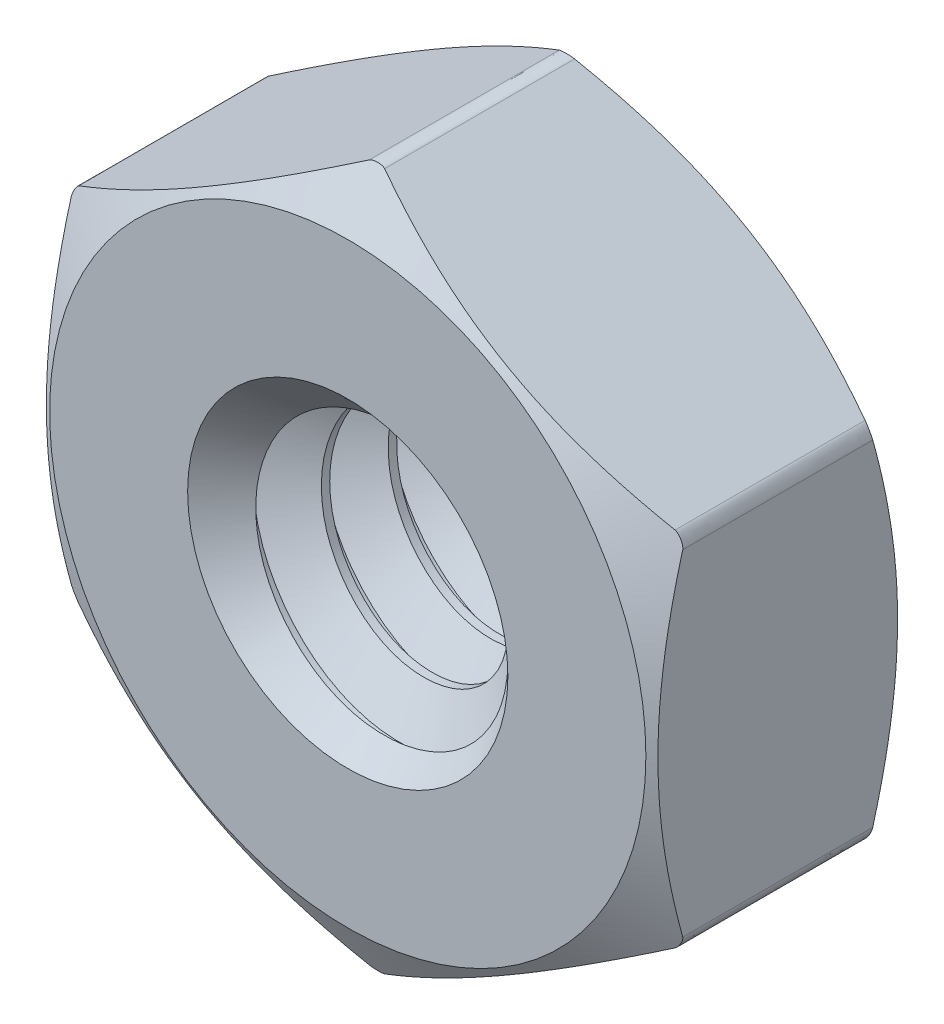
SolidWorks part; units mm, degrees
ref_plane "Front Plane" through (0, 0, 0) normal (0, 0, 1) x (1, 0, 0)
ref_plane "Top Plane" through (0, 0, 0) normal (0, 1, 0) x (1, 0, 0)
ref_plane "Right Plane" through (0, 0, 0) normal (1, 0, 0) x (0, 0, -1)
sketch "Sketch1" plane through (0, 0, 0) normal (0, 0, 1) x (1, 0, 0)
  line L0 (0, -1.8475) -> (0, 1.8475) construction
  line L1 (0, -1.8475) -> (1.6, -0.9238) construction
  line L2 (1.6, -0.9238) -> (1.6, 0.9238) construction
  line L3 (1.6, 0.9238) -> (0, 1.8475) construction
  line L4 (0, 1.8475) -> (-1.6, 0.9238) construction
  line L5 (-1.6, 0.9238) -> (-1.6, -0.9238) construction
  line L6 (-1.6, -0.9238) -> (0, -1.8475) construction
  line L7 (-1.6, 0) -> (1.6, 0) construction
  line L8 (0, 0) -> (0.4, -0.6928) construction
  circle A0 centre (0, 0) radius 1.6 construction
  circle A1 centre (0, 0) radius 0.8 construction
  point P11 (0, 0)
  point P12 (0, -0.8)
  point P14 (0.8, 0)
  point P15 (0, 0.8)
  point P16 (-0.8, 0)
  point P19 (0.4, -0.6928)
  dimension "Thread Diameter" = 1.6
  dimension "Width" = 3.2
  dimension "D1" = 30
sketch "Sketch2" plane through (0, 0, 0) normal (1, 0, 0) x (0, 0, -1)
  line L0 (0, -1.6) -> (0, 1.6) construction
  line L1 (-0.65, 1.6) -> (0.65, 1.6) construction
  line L2 (-0.65, 1.6) -> (-0.65, -1.6) construction
  line L3 (-0.65, -1.6) -> (0.65, -1.6) construction
  line L4 (0.65, 1.6) -> (0.65, -1.6) construction
  line L5 (0.65, 0) -> (-0.65, 0) construction
  line L8 (-0.65, 0.8) -> (0.65, 0.8) construction
  line L9 (-0.65, -0.8) -> (0.65, -0.8) construction
  line L10 (-0.9781, 0.8379) -> (-0.6281, 0.8379) construction
  line L11 (-0.6281, 0.8379) -> (-0.8031, 0.5348) construction
  line L12 (-0.8031, 0.5348) -> (-0.9781, 0.8379) construction
  line L13 (-0.9672, 0.8189) -> (-0.6391, 0.8189) construction
  line L14 (-0.9563, 0.8) -> (-0.65, 0.8) construction
  line L15 (-0.825, 0.5727) -> (-0.7813, 0.5727) construction
  line L16 (-0.8031, 0.5727) -> (-0.8031, 0.5348) construction
  line L17 (-0.8031, 0.8379) -> (-0.8031, 0.8) construction
  point P8 (0, 0)
  point P29 (-0.8031, 0.8189)
  dimension "Height" = 1.3
  dimension "Thread Pitch" = 0.35
  dimension "D2" = 0.0437
sketch "Sketch3" plane through (0, 0, 0) normal (0, 0, 1) x (1, 0, 0)
  line L1 (0, -1.8475) -> (1.6, -0.9238)
  line L2 (1.6, -0.9238) -> (1.6, 0.9238)
  line L3 (1.6, 0.9238) -> (0, 1.8475)
  line L4 (0, 1.8475) -> (-1.6, 0.9238)
  line L5 (-1.6, 0.9238) -> (-1.6, -0.9238)
  line L6 (-1.6, -0.9238) -> (0, -1.8475)
  circle A0 centre (0, 0) radius 1.6 construction
  circle A1 centre (0, 0) radius 0.5727
extrude "Boss-Extrude1" add sketch "Sketch3" along normal up to vertex (0.65 mm away) and the other way up to vertex (0.65 mm away) up to point (0, 0, 0.65) other way up to point (0, 0, -0.65)
sketch "Sketch4" plane through (0, 0, 0) normal (0, 0, 1) x (1, 0, 0)
  circle A0 centre (0, 0) radius 1.56
  dimension "D1" = 3.12
extrude "Cut-Extrude1" cut sketch "Sketch4" against normal through all draft 60 from vertex flip side to cut starting at point (0, 0, 0.65)
extrude "Cut-Extrude2" cut sketch "Sketch4<2>" along normal through all draft 60 from vertex flip side to cut starting at point (0, 0, -0.65)
sketch "Sketch4<2>" plane through (0, 0, 0) normal (0, 0, 1) x (1, 0, 0) same geometry as "Sketch4"
chamfer "Chamfer1" distance 0.2188 angle 45 2 edges at (0.5727, 0, -0.65) (0.5727, 0, 0.65)
fillet "Fillet1" radius 0.08 6 edges at (-1.6, -0.9238, 0) (-1.6, 0.9238, 0) (0, -1.8475, 0) (1.6, -0.9238, 0) (0, 1.8475, 0) (1.6, 0.9238, 0) conic rho 0.3
ref_axis "Center Axis 1" through (0, 0, -13.8025) along (0, 0, 1)
sketch "Sketch5" plane through (0, 0, 0) normal (0, 0, 1) x (1, 0, 0)
  circle A0 centre (0, 0) radius 0.8 construction
  circle A1 centre (0, 0) radius 0.8
extrude "Cut-Extrude3" cut sketch "Sketch5" against normal through all both and the other way through all
sketch "Sketch6" plane through (0, 0, 0.65) normal (0, 0, 1) x (1, 0, 0)
  circle A0 centre (0, 0) radius 0.8 construction
  circle A1 centre (0, 0) radius 0.8
curve "Helix/Spiral1" pitch 0.35 height 1.65 radius 0.8 centre (0, 0, 0.65) axis (0, 0, -1) start towards (0, 1, 0)
sketch "Sketch7" plane through (0, 0, 0) normal (1, 0, 0) x (0, 0, -1)
  line L0 (-0.9672, 0.8189) -> (-0.6391, 0.8189)
  line L1 (-0.6391, 0.8189) -> (-0.7813, 0.5727)
  line L2 (-0.7813, 0.5727) -> (-0.825, 0.5727)
  line L3 (-0.825, 0.5727) -> (-0.9672, 0.8189)
sweep "Sweep1" add profiles "Sketch7" path "Helix/Spiral1"
sketch "Sketch8" plane through (0, 0, 0.65) normal (0, 0, 1) x (1, 0, 0)
  circle A0 centre (0, 0) radius 0.8379
extrude "Cut-Extrude4" cut sketch "Sketch8" against normal through all draft 45 and the other way through all
sketch "Sketch9" plane through (0, 0, -0.65) normal (0, 0, -1) x (-1, 0, 0)
  circle A1 centre (0, 0) radius 0.8379
  circle A2 centre (0, 0) radius 0.8379
  dimension "D1" = 0
extrude "Cut-Extrude5" cut sketch "Sketch9" against normal through all draft 45 and the other way through all
equation "\"D2@Sketch2\" = \"Thread Pitch@Sketch2\" / 8"
equation "\"D1@Chamfer1\"=\"Thread Pitch@Sketch2\"*.625"
equation "\"D1@Sketch4\"=\"Width@Sketch1\"*.975"
equation "\"D1@Fillet1\"=\"Width@Sketch1\"*.025"
equation "\"D4@Helix/Spiral1\"=\"Thread Pitch@Sketch2\""
equation "\"D3@Helix/Spiral1\"=\"Height@Sketch2\"+\"Thread Pitch@Sketch2\""
